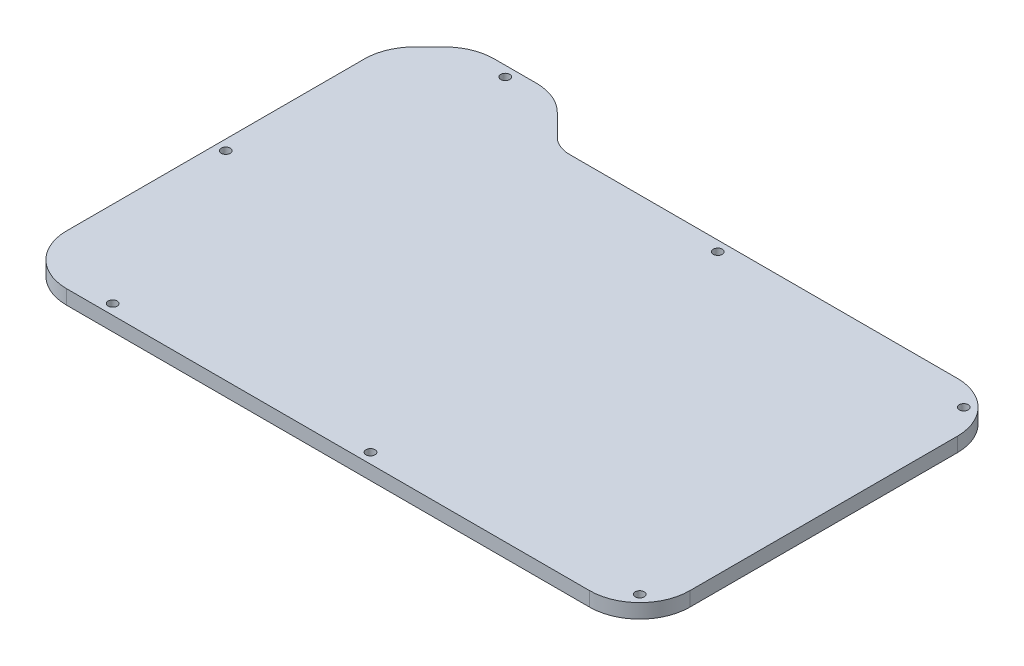
SolidWorks part; units mm, degrees
ref_plane "Front Plane" through (0, 0, 0) normal (0, 0, 1) x (1, 0, 0)
ref_plane "Top Plane" through (0, 0, 0) normal (0, 1, 0) x (1, 0, 0)
ref_plane "Right Plane" through (0, 0, 0) normal (1, 0, 0) x (0, 0, -1)
sketch "Sketch1" plane through (0, 0, 0) normal (0, 1, 0) x (1, 0, 0)
  line L7 (11.9909, 30.0462) -> (-73.9577, 30.0462)
  line L8 (-78.6246, 31.9793) -> (-83.4404, 36.7951)
  line L9 (-91.2893, 40.0462) -> (-100.6523, 40.0462)
  line L10 (-108.5012, 36.7951) -> (-111.7815, 33.5148)
  line L11 (-115.0326, 25.666) -> (-115.0326, -40.3538)
  line L12 (-103.9326, -51.4538) -> (11.9909, -51.4538)
  line L13 (23.0909, -40.3538) -> (23.0909, 18.9462)
  circle A0 centre (-95.9708, 37.7962) radius 1
  circle A8 centre (-95.9708, -49.2038) radius 1
  circle A9 centre (-38.861, -49.1808) radius 1
  circle A10 centre (18.2488, -46.6117) radius 1
  circle A11 centre (18.2488, 25.2041) radius 1
  circle A12 centre (-38.861, 27.7962) radius 1
  circle A13 centre (-112.7826, -7.3439) radius 1
  arc A14 (-78.6246, 31.9793) -> (-73.9577, 30.0462) centre (-73.9577, 36.6462) ccw
  arc A15 (-83.4404, 36.7951) -> (-91.2893, 40.0462) centre (-91.2893, 28.9462) ccw
  arc A16 (-100.6523, 40.0462) -> (-108.5012, 36.7951) centre (-100.6523, 28.9462) ccw
  arc A17 (-111.7815, 33.5148) -> (-115.0326, 25.666) centre (-103.9326, 25.666) ccw
  arc A18 (-115.0326, -40.3538) -> (-103.9326, -51.4538) centre (-103.9326, -40.3538) ccw
  arc A19 (11.9909, -51.4538) -> (23.0909, -40.3538) centre (11.9909, -40.3538) ccw
  arc A20 (23.0909, 18.9462) -> (11.9909, 30.0462) centre (11.9909, 18.9462) ccw
extrude "Boss-Extrude1" add sketch "Sketch1" along normal blind 3.175
